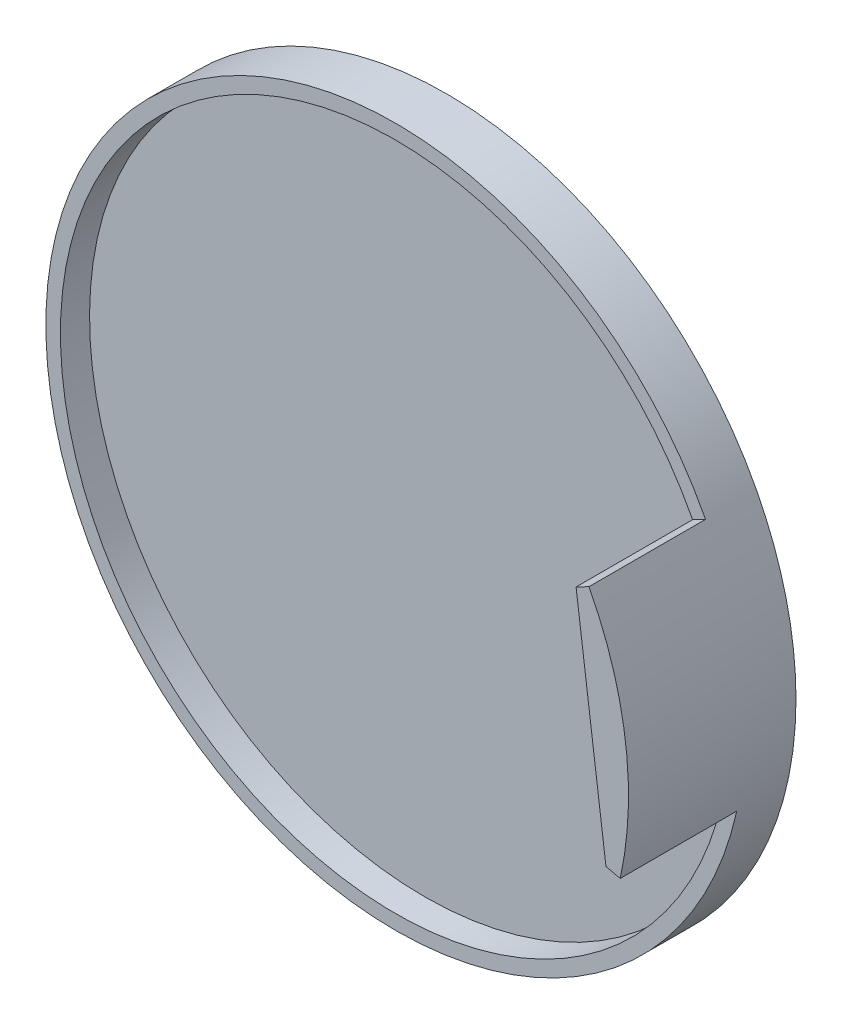
SolidWorks part; units mm, degrees
ref_plane "Front Plane" through (0, 0, 0) normal (1, 0, 0) x (0, 1, 0)
ref_plane "Top Plane" through (0, 0, 0) normal (0, 0, 1) x (0, 1, 0)
ref_plane "Right Plane" through (0, 0, 0) normal (0, 1, 0) x (-1, 0, 0)
sketch "Sketch1" plane through (0, 0, 0) normal (0, 0, 1) x (0, 1, 0)
  circle A0 centre (0, 0) radius 48
  dimension "D1" = 96
extrude "Boss-Extrude1" add sketch "Sketch1" along normal blind 3
sketch "Sketch2" plane through (0, 0, 3) normal (0, 0, 1) x (1, 0, 0)
  circle A0 centre (0, 0) radius 48
  circle A1 centre (0, 0) radius 46
  circle A2 centre (0, 0) radius 48 construction
  circle M3 centre (0, 0) radius 48
extrude "Boss-Extrude2" add sketch "Sketch2" along normal blind 4 contours A1 M3 region at (-46.6424, 0, 3)
sketch "Sketch3" plane through (0, 0, 3) normal (0, 0, 1) x (1, 0, 0)
  line L0 (0, 0) -> (46.862, -10.3899) construction
  line L1 (0, 0) -> (42.5769, 22.1632) construction
  line L2 (42.5769, 22.1632) -> (40.8029, 21.2397)
  line L3 (44.9094, -9.957) -> (46.862, -10.3899)
  line L4 (40.8029, 21.2397) -> (44.9094, -9.957)
  circle A0 centre (0, 0) radius 48
  circle A1 centre (0, 0) radius 48 construction
  circle A2 centre (0, 0) radius 46
  circle M3 centre (0, 0) radius 46
extrude "Boss-Extrude3" add sketch "Sketch3" along normal blind 20 contours L3 A0 L2 M3 | L4 M3 region at (45.6643, 6.011, 3) region at (43.9592, 5.7866, 3)
fillet "Fillet1" radius 2 1 edges at (42.8562, 5.6414, 3)
